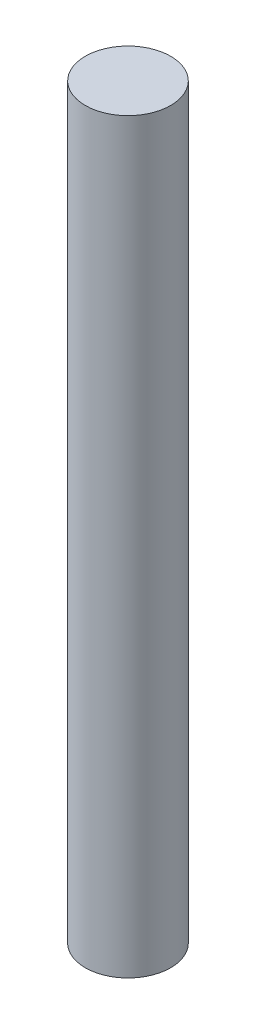
SolidWorks part; units mm, degrees
ref_plane "Front Plane" through (0, 0, 0) normal (0, 0, 1) x (1, 0, 0)
ref_plane "Top Plane" through (0, 0, 0) normal (0, 1, 0) x (1, 0, 0)
ref_plane "Right Plane" through (0, 0, 0) normal (1, 0, 0) x (0, 0, -1)
sketch "Sketch1" plane through (0, 0, 0) normal (0, 1, 0) x (1, 0, 0)
  circle A0 centre (0, 0) radius 1
  dimension "D1" = 2
extrude "Boss-Extrude1" add sketch "Sketch1" along normal blind 12.7 and the other way blind 4.8
